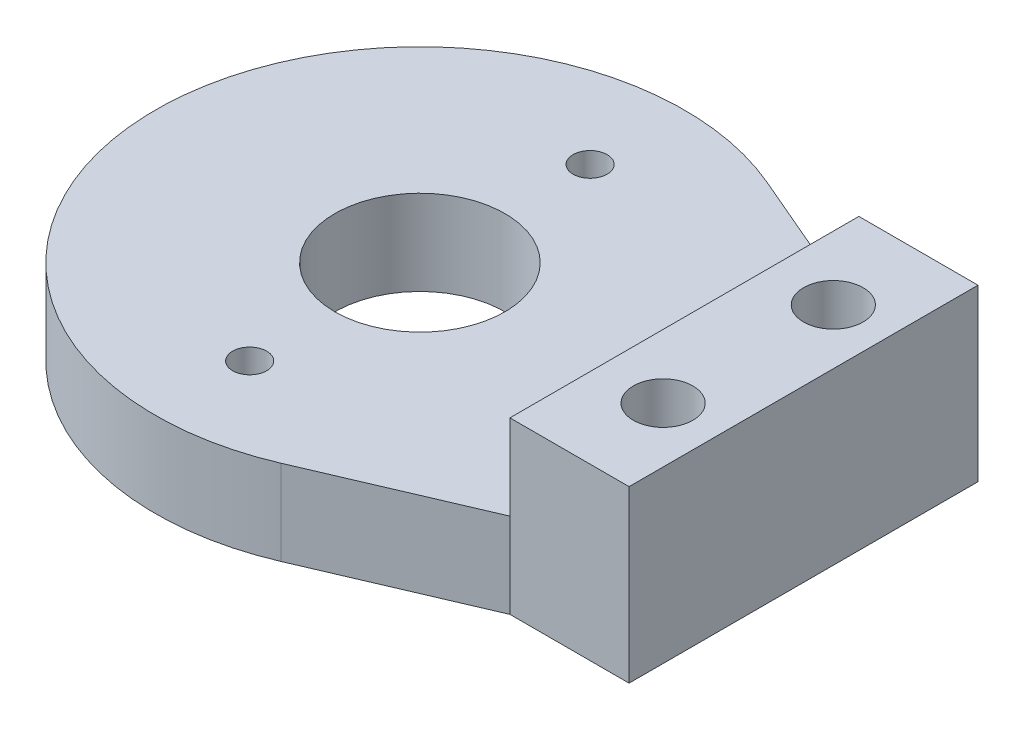
SolidWorks part; units mm, degrees
ref_plane "Front" through (0, 0, 0) normal (0, 0, 1) x (1, 0, 0)
ref_plane "Top" through (0, 0, 0) normal (0, 1, 0) x (1, 0, 0)
ref_plane "Right" through (0, 0, 0) normal (1, 0, 0) x (0, 0, -1)
sketch "Sketch1" plane through (0, 0, 0) normal (0, 1, 0) x (1, 0, 0)
  line L1 (0, 0) -> (7, 0)
  line L2 (0, 0) -> (0, -20.5)
  line L3 (0, -20.5) -> (7, -20.5)
  line L4 (7, 0) -> (7, -20.5)
  dimension "D1" = 7
  dimension "D2" = 20.5
extrude "mountingBase" add sketch "Sketch1" along normal blind 10
sketch "Sketch2" plane through (0, 10, 0) normal (0, 1, 0) x (1, 0, 0)
  line L0 (0, 0) -> (0, -20.5) construction
  line L1 (0, -10.25) -> (7, -10.25) construction
  line L2 (7, -20.5) -> (7, 0) construction
  line L3 (7, 0) -> (0, 0) construction
  circle A0 centre (3.75, -5.25) radius 1.75
  circle A1 centre (3.75, -15.25) radius 1.75
  dimension "D2" = 3.5
  dimension "D1" = 3.75
  dimension "D3" = 5.25
extrude "mountingHoles" cut sketch "Sketch2" against normal blind 10
sketch "Sketch3" plane through (0, 0, 0) normal (0, 1, 0) x (1, 0, 0)
  line L0 (0, 0) -> (0, -20.5) construction
  line L1 (0, 0) -> (-9.4224, 4.0351)
  line L2 (0, -20.5) -> (-9.4224, -24.5351)
  line L3 (0, 0) -> (0, -20.5)
  arc A0 (-9.4224, 4.0351) -> (-9.4224, -24.5351) centre (-15.5398, -10.25) ccw
  point P4 (0, -10.25)
  dimension "D1" = 15.5398
extrude "hornTab" add sketch "Sketch3" along normal blind 5
sketch "Sketch4" plane through (0, 5, 0) normal (0, 1, 0) x (1, 0, 0)
  line L0 (-15.5398, -10.25) -> (-31.0797, -10.25) construction
  circle A0 centre (-15.5398, -10.25) radius 15.5398 construction
  arc A1 (-9.4224, 4.0351) -> (-9.4224, -24.5351) centre (-15.5398, -10.25) ccw construction
  circle A2 centre (-15.5398, -0.25) radius 1
  circle A3 centre (-15.5398, -20.25) radius 1
  circle A4 centre (-15.5398, -10.25) radius 5
  dimension "D1" = 2
  dimension "D3" = 10
  dimension "D2" = 10
extrude "hornMountingHoles" cut sketch "Sketch4" against normal blind 5
